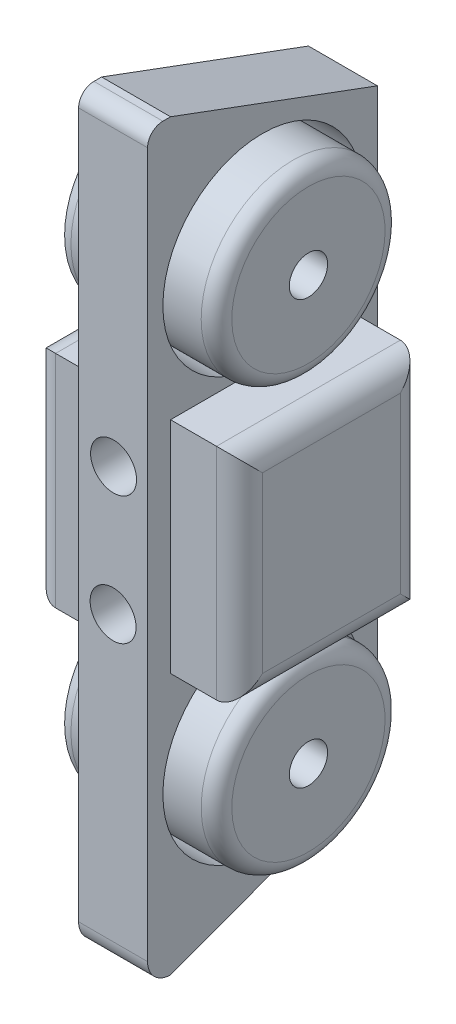
SolidWorks part; units mm, degrees
ref_plane "Front Plane" through (0, 0, 0) normal (0, 0, 1) x (1, 0, 0)
ref_plane "Top Plane" through (0, 0, 0) normal (0, 1, 0) x (1, 0, 0)
ref_plane "Right Plane" through (0, 0, 0) normal (1, 0, 0) x (0, 0, -1)
sketch "Sketch1" plane through (0, 0, 0) normal (0, 0, 1) x (1, 0, 0)
  line L1 (0, 0) -> (9, 0)
  line L2 (0, 0) -> (0, 100)
  line L3 (0, 100) -> (9, 100)
  line L4 (9, 0) -> (9, 100)
  dimension "D1" = 9
  dimension "D2" = 100
extrude "Boss-Extrude1" add sketch "Sketch1" along normal blind 3 contours L2 L1 L4 L3
fillet "Fillet1" radius 3 2 edges at (4.5, 0, 3) (4.5, 100, 3)
sketch "Sketch2" plane through (9, 0, 0) normal (1, 0, 0) x (0, 0, -1)
  line L1 (0, 100) -> (-3, 100)
  line L2 (0, 100) -> (0, 97)
  line L3 (0, 97) -> (-3, 97)
  line L4 (-3, 100) -> (-3, 97)
extrude "Cut-Extrude1" cut sketch "Sketch2" against normal blind 13
sketch "Sketch3" plane through (9, 0, 0) normal (1, 0, 0) x (0, 0, -1)
  line L1 (0, 97) -> (27, 97)
  line L2 (0, 97) -> (0, 0)
  line L3 (0, 0) -> (27, 0)
  line L4 (27, 97) -> (27, 0)
  dimension "D1" = 27
extrude "Boss-Extrude2" add sketch "Sketch3" against normal blind 9
sketch "Sketch4" plane through (9, 0, 0) normal (1, 0, 0) x (0, 0, -1)
  line L0 (27, 97) -> (27, 87)
  line L1 (-3, 97) -> (0, 97)
  line L2 (-3, 97) -> (-3, 0)
  line L3 (-3, 0) -> (0, 0)
  line L4 (0, 97) -> (0, 0)
  line L5 (27, 0) -> (27, 97) construction
  line L6 (27, 0) -> (27, 10)
  line L7 (27, 10) -> (0, 0)
  line L8 (27, 87) -> (0, 97)
  line L9 (27, 87) -> (27, 10)
  line L10 (0, 97) -> (27, 97)
  line L11 (27, 0) -> (0, 0)
  line M2 (0, 0) -> (27, 0)
  line M3 (27, 0) -> (27, 97)
  line M4 (27, 97) -> (-3, 97)
  dimension "D1" = 10
  dimension "D2" = 10
extrude "Cut-Extrude2" cut sketch "Sketch4" against normal blind 9 contours L8 M3 M4 | L7 M3 M2 region at (9, 93.6667, -18) region at (9, 3.3333, -18)
sketch "Sketch7" plane through (9, 0, 0) normal (1, 0, 0) x (0, 0, -1)
  line L0 (0, 97) -> (0, 0)
  line L1 (27, 10) -> (24, 8.8889)
  line L2 (27, 10) -> (0, 0) construction
  line L3 (24, 8.8889) -> (24, 88.1111)
  line L4 (27, 87) -> (0, 97) construction
  line L5 (24, 88.1111) -> (0, 97)
  line L6 (24, 8.8889) -> (0, 0)
  line L7 (24, 88.1111) -> (0, 88.1111)
  line L8 (0, 88.1111) -> (0, 64.1111)
  line L9 (0, 64.1111) -> (24, 64.1111)
  line L10 (24, 64.1111) -> (24, 88.1111)
  line L11 (24, 8.8889) -> (0, 8.8889)
  line L12 (0, 8.8889) -> (0, 32.8889)
  line L13 (0, 32.8889) -> (24, 32.8889)
  line L14 (24, 32.8889) -> (24, 8.8889)
  line L15 (0, 88.1111) -> (24, 64.1111)
  line L16 (0, 8.8889) -> (24, 32.8889)
  circle A0 centre (12, 76.1111) radius 12
  circle A1 centre (12, 20.8889) radius 12
  dimension "D1" = 3
  dimension "D2" = 24
  dimension "D3" = 24
  dimension "D4" = 24
  dimension "D5" = 24
extrude "Boss-Extrude5" add sketch "Sketch7" along normal blind 6 contours A0 L15 | L15 A0 | A1 L16 | L16 A1 region at (9, 72.5098, -8.3987) region at (9, 79.7124, -15.6013) region at (9, 24.4902, -8.3987) region at (9, 17.2876, -15.6013)
sketch "Sketch8" plane through (0, 0, 0) normal (-1, 0, 0) x (0, 0, 1)
  line L0 (0, 97) -> (0, 0)
  line L1 (-27, 87) -> (0, 97) construction
  line L2 (-27, 87) -> (-24, 88.1111)
  line L3 (-24, 88.1111) -> (-24, 8.8889)
  line L4 (-27, 10) -> (0, 0) construction
  line L5 (0, 8.8889) -> (0, 32.8889)
  line L6 (0, 32.8889) -> (-24, 32.8889)
  line L7 (-24, 32.8889) -> (-24, 8.8889)
  line L8 (-24, 88.1111) -> (0, 88.1111)
  line L9 (0, 88.1111) -> (0, 64.1111)
  line L10 (0, 64.1111) -> (-24, 64.1111)
  line L11 (-24, 64.1111) -> (-24, 88.1111)
  line L12 (-24, 8.8889) -> (0, 8.8889)
  line L13 (-24, 88.1111) -> (0, 64.1111)
  line L14 (-24, 32.8889) -> (0, 8.8889)
  circle A0 centre (-12, 76.1111) radius 12
  circle A1 centre (-12, 20.8889) radius 12
  dimension "D1" = 3
  dimension "D2" = 24
  dimension "D3" = 24
  dimension "D4" = 24
  dimension "D5" = 24
extrude "Boss-Extrude6" add sketch "Sketch8" along normal blind 6 contours A0 L13 | L13 A0 | A1 L14 | L14 A1 region at (0, 79.7124, -8.3987) region at (0, 72.5098, -15.6013) region at (0, 24.4902, -8.3987) region at (0, 17.2876, -15.6013)
sketch "Sketch9" plane through (-6, 0, 0) normal (-1, 0, 0) x (0, 0, 1)
  circle A0 centre (-12, 76.1111) radius 2.5
  circle A1 centre (-12, 20.8889) radius 2.5
  dimension "D1" = 5
  dimension "D2" = 5
extrude "Cut-Extrude3" cut sketch "Sketch9" against normal blind 46 contours A0 | A1
sketch "Sketch10" plane through (15, 0, 0) normal (1, 0, 0) x (0, 0, -1)
  circle A0 centre (12, 76.1111) radius 12
  circle A1 centre (12, 76.1111) radius 13
  circle A2 centre (12, 20.8889) radius 12
  circle A3 centre (12, 20.8889) radius 13
  dimension "D1" = 1
  dimension "D2" = 1
extrude "Cut-Extrude4" cut sketch "Sketch10" against normal blind 46 contours A1 | A0 | A2 | A3
sketch "Sketch11" plane through (0, 0, 0) normal (-1, 0, 0) x (0, 0, 1)
  line L0 (-27, 48.5) -> (3, 48.5)
  line L1 (-27, 10) -> (-27, 87) construction
  line L2 (3, 3) -> (3, 97) construction
  line L4 (-27, 48.5) -> (3, 48.5)
  line L5 (-27, 48.5) -> (-27, 62.7522)
  line L6 (-27, 62.7522) -> (3, 62.7522)
  line L7 (3, 48.5) -> (3, 62.7522)
  line L8 (-27, 48.5) -> (3, 48.5)
  line L9 (-27, 48.5) -> (-27, 33.9772)
  line L10 (-27, 33.9772) -> (3, 33.9772)
  line L11 (3, 48.5) -> (3, 33.9772)
  line M5 (-27, 87) -> (-27, 10)
  line M8 (3, 3) -> (3, 97)
extrude "Boss-Extrude7" add sketch "Sketch11" along normal blind 6 contours L6 L0 M5 M8 | L10 L0 M5 M8 region at (0, 55.6261, -12) region at (0, 41.2386, -12)
sketch "Sketch12" plane through (9, 0, 0) normal (1, 0, 0) x (0, 0, -1)
  line L0 (-3, 50) -> (27, 50)
  line L1 (-3, 3) -> (-3, 97) construction
  line L2 (27, 10) -> (27, 87) construction
  line L4 (-3, 50) -> (27, 50)
  line L5 (-3, 50) -> (-3, 34.0674)
  line L6 (-3, 34.0674) -> (27, 34.0674)
  line L7 (27, 50) -> (27, 34.0674)
  line L8 (27, 50) -> (-3, 50)
  line L9 (27, 50) -> (27, 62.7522)
  line L10 (27, 62.7522) -> (-3, 62.7522)
  line L11 (-3, 50) -> (-3, 62.7522)
  line M5 (-3, 97) -> (-3, 3)
  line M8 (27, 10) -> (27, 87)
extrude "Boss-Extrude8" add sketch "Sketch12" along normal blind 6 contours L10 L0 M8 M5 | L6 L0 M5 M8 region at (9, 56.3761, -12) region at (9, 42.0337, -12)
sketch "Sketch13" plane through (15, 0, 0) normal (1, 0, 0) x (0, 0, -1)
  line L0 (-3, 34.0674) -> (27, 34.0674) construction
  line L1 (27, 62.7522) -> (24, 62.7522)
  line L2 (27, 62.7522) -> (27, 34.0674)
  line L3 (27, 34.0674) -> (24, 34.0674)
  line L4 (24, 62.7522) -> (24, 34.0674)
  line L6 (-3, 62.7522) -> (0, 62.7522)
  line L7 (-3, 62.7522) -> (-3, 34.0674)
  line L8 (-3, 34.0674) -> (0, 34.0674)
  line L9 (0, 62.7522) -> (0, 34.0674)
  dimension "D1" = 3
  dimension "D2" = 3
extrude "Cut-Extrude5" cut sketch "Sketch13" against normal blind 6 contours L7 L6 L9 L8 | L2 L1 L4 L3
sketch "Sketch14" plane through (-6, 0, 0) normal (-1, 0, 0) x (0, 0, 1)
  line L0 (-27, 33.9772) -> (3, 33.9772) construction
  line L1 (3, 62.7522) -> (0, 62.7522)
  line L2 (3, 62.7522) -> (3, 33.9772)
  line L3 (3, 33.9772) -> (0, 33.9772)
  line L4 (0, 62.7522) -> (0, 33.9772)
  line L5 (-27, 62.7522) -> (3, 62.7522) construction
  line L6 (-27, 33.9772) -> (-24, 33.9772)
  line L7 (-27, 33.9772) -> (-27, 62.7522)
  line L8 (-27, 62.7522) -> (-24, 62.7522)
  line L9 (-24, 33.9772) -> (-24, 62.7522)
  dimension "D1" = 3
  dimension "D2" = 3
extrude "Cut-Extrude6" cut sketch "Sketch14" against normal blind 6
sketch "Sketch15" plane through (-6, 0, 0) normal (-1, 0, 0) x (0, 0, 1)
  line L0 (-24, 33.9772) -> (0, 33.9772) construction
  line L1 (-24, 62.7522) -> (0, 62.7522)
  line L2 (-24, 62.7522) -> (-24, 33.9772)
  line L3 (-24, 33.9772) -> (0, 33.9772)
  line L4 (0, 62.7522) -> (0, 33.9772)
  line L5 (0, 62.7522) -> (0, 33.9772) construction
extrude "Boss-Extrude9" add sketch "Sketch15" along normal mid plane 6
sketch "Sketch16" plane through (15, 0, 0) normal (1, 0, 0) x (0, 0, -1)
  line L1 (0, 62.7522) -> (24, 62.7522)
  line L2 (0, 62.7522) -> (0, 34.0674)
  line L3 (0, 34.0674) -> (24, 34.0674)
  line L4 (24, 62.7522) -> (24, 34.0674)
extrude "Boss-Extrude10" add sketch "Sketch16" along normal mid plane 6
fillet "Fillet2" radius 2 2 edges at (-6, 76.1111, 0) (15, 88.1111, -12)
fillet "Fillet3" radius 2 2 edges at (-6, 20.8889, 0) (15, 32.8889, -12)
fillet "Fillet4" radius 2 1 edges at (4.5, 97, 3)
sketch "Sketch5" plane through (9, 0, 0) normal (1, 0, 0) x (0, 0, -1)
  line L2 (27, 10) -> (27, 87) construction
  line L10 (27, 37) -> (27, 10)
  line L15 (27, 60) -> (27, 87)
  circle A0 centre (13.5, 23.5) radius 13.5
  circle A1 centre (13.5, 73.5) radius 13.5
sketch "Sketch18" plane through (0, 0, 3) normal (0, 0, 1) x (1, 0, 0)
  line L0 (0, 62.7522) -> (9, 62.7522)
  line L1 (9, 60) -> (9, 87) construction
  line L2 (9, 62.7522) -> (9, 34.0674)
  line L3 (9, 34.0674) -> (0, 33.9772)
  line L4 (0, 3) -> (0, 95) construction
  line L5 (0, 62.7522) -> (0, 33.9772) construction
  line L6 (0, 33.9772) -> (0, 62.7522)
  line L7 (4.5, 62.7522) -> (4.5601, 56.7522)
  line L8 (4.5, 34.0223) -> (4.5, 40.0223)
  circle A0 centre (4.5, 40.0223) radius 3
  circle A1 centre (4.5601, 56.7522) radius 3
  dimension "D3" = 6
  dimension "D4" = 6
  dimension "D1" = 6
  dimension "D2" = 6
extrude "Cut-Extrude7" cut sketch "Sketch18" against normal blind 40 contours A1 | A0 region at (2.4387, 42.0836, 3) region at (6.6111, 58.8238, 3)
fillet "Fillet5" radius 3 8 edges at (18, 62.7522, -12) (18, 34.0674, -12) (18, 48.4098, 0) (18, 48.4098, -24) (-9, 62.7522, -12) (-9, 33.9772, -12) (-9, 48.3647, -24) (-9, 48.3647, 0)
sketch "Sketch19" plane through (18, 0, 0) normal (1, 0, 0) x (0, 0, -1)
  line L0 (27, 97.1353) -> (27, 0)
  line L1 (-3.0053, 0) -> (-3.0053, 97.1353)
  line L2 (-3.0053, 97.1353) -> (27, 97.1353)
  line L3 (27, 0) -> (-3.0053, 0)
  line L4 (0, 97) -> (0, 0)
  line L5 (27, 0) -> (-3.0053, 0)
  line L6 (27, 0) -> (27, 97.1353)
  line L7 (27, 97.1353) -> (-3.0053, 97.1353)
  line L8 (-3.0053, 0) -> (-3.0053, 97.1353)
  line L9 (27, 97.1353) -> (27, 87)
  dimension "D1" = 3.0053
  dimension "D2" = 10.1353
